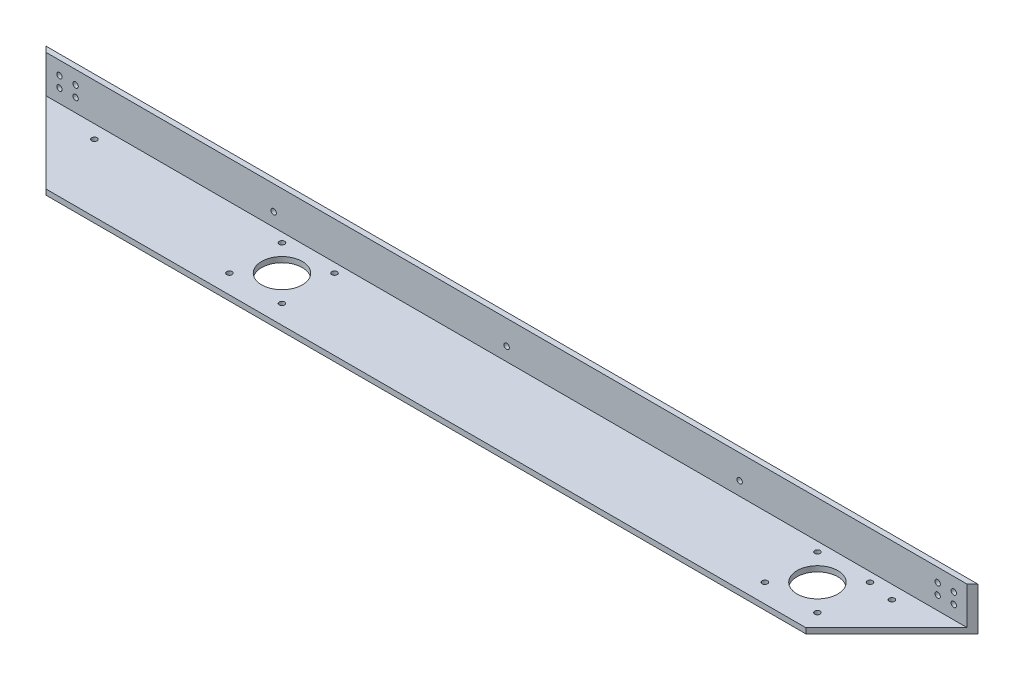
SolidWorks part; units mm, degrees
ref_plane "Front Plane" through (0, 0, 0) normal (0, 0, 1) x (1, 0, 0)
ref_plane "Top Plane" through (0, 0, 0) normal (0, 1, 0) x (1, 0, 0)
ref_plane "Right Plane" through (0, 0, 0) normal (1, 0, 0) x (0, 0, -1)
sketch "Sketch1" plane through (0, 0, 0) normal (1, 0, 0) x (0, 0, -1)
  line L0 (0, 0) -> (-50.8, 0)
  line L1 (-50.8, 0) -> (-50.8, 3.175)
  line L2 (-50.8, 3.175) -> (-3.175, 3.175)
  line L3 (-3.175, 3.175) -> (-3.175, 25.4)
  line L4 (-3.175, 25.4) -> (0, 25.4)
  line L5 (0, 25.4) -> (0, 0)
  dimension "LHeight" = 25.4
  dimension "LWidth" = 50.8
  dimension "LMaterialThickness" = 3.175
  dimension "D1" = 47.625
  dimension "D2" = 22.225
  dimension "D3" = 3.175
extrude "Boss-Extrude1" add sketch "Sketch1" along normal blind 550
chamfer "Chamfer7" distance 50.8 angle 45 1 edges at (0, 1.5875, 50.8)
chamfer "Chamfer8" distance 50.8 angle 45 1 edges at (550, 1.5875, 50.8)
sketch "BotthomHoles-Sketch2" plane through (0, 3.175, 0) normal (0, 1, 0) x (1, 0, 0)
  line L0 (546.825, -3.175) -> (3.175, -3.175) construction
  line L1 (550, 0) -> (0, 0) construction
  circle A0 centre (479.425, -24.175) radius 12
  circle A2 centre (463.925, -8.675) radius 1.5875
  circle A3 centre (494.925, -8.675) radius 1.5875
  circle A6 centre (463.925, -39.675) radius 1.5875
  circle A7 centre (494.925, -39.675) radius 1.5875
  circle A8 centre (39.6875, -11.1125) radius 1.5875
  circle A9 centre (510.3125, -11.1125) radius 1.5875
  circle A10 centre (178.925, -39.675) radius 1.5875
  circle A11 centre (147.925, -39.675) radius 1.5875
  circle A12 centre (178.925, -8.675) radius 1.5875
  circle A13 centre (147.925, -8.675) radius 1.5875
  circle A14 centre (163.425, -24.175) radius 12
  dimension "D9" = 3.175
  dimension "D10" = 24
  dimension "D13" = 3.175
  dimension "D2" = 8.675
  dimension "D5" = 15.5
  dimension "D6" = 31
  dimension "D7" = 15.5
  dimension "D8" = 31
  dimension "D11" = 21
  dimension "D3" = 70.575
  dimension "D4" = 11.1125
  dimension "D12" = 39.6875
  dimension "D14" = 39.6875
  dimension "D15" = 31
  dimension "D16" = 15.5
  dimension "D17" = 316
extrude "BottomHoles-Cut-Extrude1" cut sketch "BotthomHoles-Sketch2" against normal through all
sketch "SideHoles-Sketch3" plane through (0, 0, 0) normal (0, 0, -1) x (-1, 0, 0)
  line L0 (-550, 0) -> (-550, 25.4) construction
  circle A0 centre (-538.8875, 17.4625) radius 1.5875
  circle A1 centre (-529.3625, 17.4625) radius 1.5875
  circle A2 centre (-538.8875, 11.1125) radius 1.5875
  circle A3 centre (-529.3625, 11.1125) radius 1.5875
  circle A4 centre (-11.1125, 11.1125) radius 1.5875
  circle A5 centre (-20.6375, 11.1125) radius 1.5875
  circle A6 centre (-20.6375, 17.4625) radius 1.5875
  circle A7 centre (-11.1125, 17.4625) radius 1.5875
  circle A8 centre (-412.5, 11.1125) radius 1.5875
  circle A9 centre (-275, 11.1125) radius 1.5875
  circle A10 centre (-137.5, 11.1125) radius 1.5875
  dimension "D4" = 11.1125
  dimension "D7" = 3.175
  dimension "D1" = 11.1125
  dimension "D2" = 20.6375
  dimension "D3" = 7.9375
  dimension "D5" = 11.1125
  dimension "D6" = 20.6375
  dimension "D8" = 137.5
  dimension "D9" = 137.5
  dimension "D10" = 137.5
extrude "SideHoles-Cut-Extrude2" cut sketch "SideHoles-Sketch3" against normal through all
equation "\"LowerRailWidth\"= 2.00in"
equation "\"LowerRailHeight\"= 1.00in"
equation "\"RailThickness\"= .125in'Spec"
equation "\"SideRailHoleY1FromEdge\"= \"HoleOffsetFromEdge\""
equation "\"SideRailHoleX1FromSide\"= \"HoleOffsetFromSide\""
equation "\"StepperHoleDiameter\"= 24mm"
equation "\"StepperMountingHoleDiameter\"= 3.175mm"
equation "\"SideRailLength\"= 550mm"
equation "\"StepperMountingHoleDistance\"= 31mm'Spec"
equation "\"VSWidth\"= 1.25in'Spec"
equation "\"StepperMountingHoleOffsetFromLeftOrRightSide\"= \"StepperMountingHoleOffsetFromItsSide\" + \"RailThickness\""
equation "\"HoleOffsetFromEdge\"= \"RailThickness\" * 2.5"
equation "\"HoleOffsetFromSide\"= \"RailThickness\" * 3.5"
equation "\"StepperMountingHoleOffsetFromItsSide\"= 5.5mm'Spec"
equation "\"SideRailHoleX2FromSide\"= \"VSWidth\" - \"HoleOffsetFromEdge\" - \"RailThickness\"'Equals 20.6375"
equation "\"FasteningHoleDiameter\"= .125in"
equation "\"SideRailHoleY2FromSide\"= \"HoleOffsetFromSide\""
equation "\"LHeight@Sketch1\"=\"LowerRailHeight\""
equation "\"LWidth@Sketch1\"=\"LowerRailWidth\""
equation "\"D1@Chamfer7\"=\"LowerRailWidth\""
equation "\"D1@Chamfer8\"=\"LowerRailWidth\""
equation "\"D2@BotthomHoles-Sketch2\" = \"StepperMountingHoleOffsetFromLeftOrRightSide\""
equation "\"D5@BotthomHoles-Sketch2\" = \"StepperMountingHoleDistance\" / 2"
equation "\"D6@BotthomHoles-Sketch2\" = \"StepperMountingHoleDistance\""
equation "\"D7@BotthomHoles-Sketch2\" = \"StepperMountingHoleDistance\" / 2"
equation "\"D8@BotthomHoles-Sketch2\" = \"StepperMountingHoleDistance\""
equation "\"D9@BotthomHoles-Sketch2\" = \"StepperMountingHoleDiameter\""
equation "\"D10@BotthomHoles-Sketch2\" = \"StepperHoleDiameter\""
equation "\"D1@SideHoles-Sketch3\" = \"SideRailHoleX1FromSide\""
equation "\"D2@SideHoles-Sketch3\" = \"SideRailHoleX2FromSide\""
equation "\"D3@SideHoles-Sketch3\" = \"SideRailHoleY1FromEdge\""
equation "\"D4@SideHoles-Sketch3\" = \"SideRailHoleY2FromSide\""
equation "\"D7@SideHoles-Sketch3\" = \"FasteningHoleDiameter\""
equation "\"D1@Boss-Extrude1\"=\"SideRailLength\""
equation "\"D5@SideHoles-Sketch3\"=\"SideRailHoleX1FromSide\""
equation "\"D6@SideHoles-Sketch3\"=\"SideRailHoleX2FromSide\""
equation "\"BedOverlap\"= 20mm"
equation "\"BedThirdSize\"= 70mm"
equation "\"BedInnerSquareWidth\"= \"BedThirdSize\" * 3'Equals 210"
equation "\"BedInnerSquareLength\"= \"BedInnerSquareWidth\""
equation "\"BedLWidth\"= \"BedThirdSize\" + \"BedOverlap\"'Equals 90"
equation "\"BedLength\"= \"BedInnerSquareLength\" + \"BedLWidth\" * 2 - \"BedOverlap\" * 2 + \"BedIncreasedByLength\"'Equals 350"
equation "\"DistanceBetweenFrontToBackStepperHoles\"= \"BedLength\" - \"DistanceFromBedFrontToFirstLeftStepperHole\"'Equals 316"
equation "\"D3@BotthomHoles-Sketch2\"=\"DistanceFromFrontSideToFirstLeftStepperHole\""
equation "\"DistanceFromBedFrontToFirstLeftStepperHole\"= \"LeadScrewNutPadSize\" + 10mm'Equals 34"
equation "\"DistanceFromFrontSideToBedFront\"= \"RailThickness\" + \"BeltTensionerDepth\" + 10mm'Equals 36.575"
equation "\"20TGT2PulleyDiameter\"= 17.9mm'Spec"
equation "\"BeltTensionerBackWallThickness\"= 4mm"
equation "\"BeltTensionerSpaceBetweenPulleyAndWall\"= 1.5mm"
equation "\"BeltTensionerInnerDepth\"= \"20TGT2PulleyDiameter\" + \"BeltTensionerSpaceBetweenPulleyAndWall\""
equation "\"BeltTensionerDepth\"= \"BeltTensionerBackWallThickness\" + \"BeltTensionerInnerDepth\"'Equals 23.4"
equation "\"BedIncreasedByLength\"= 0mm"
equation "\"LowerCornerBlockWidth\"= \"LowerRailWidth\" - \"RailThickness\" * 2'Room for left front stepper"
equation "\"D4@BotthomHoles-Sketch2\"=\"LowerCornerBlockY1FromSide\""
equation "\"D12@BotthomHoles-Sketch2\"=\"LowerCornerBlockX1FromSide\""
equation "\"D13@BotthomHoles-Sketch2\"=\"FasteningHoleDiameter\""
equation "\"D14@BotthomHoles-Sketch2\"=\"LowerCornerBlockX1FromSide\""
equation "\"LowerCornerBlockX1FromSide\"= \"LowerCornerBlockWidth\" - \"HoleOffsetFromEdge\" + \"RailThickness\""
equation "\"LowerCornerBlockY1FromSide\"= \"HoleOffsetFromSide\""
equation "\"D15@BotthomHoles-Sketch2\"=\"StepperMountingHoleDistance\""
equation "\"D16@BotthomHoles-Sketch2\"=\"StepperMountingHoleDistance\"/2"
equation "\"D17@BotthomHoles-Sketch2\"=\"DistanceBetweenFrontToBackStepperHoles\""
equation "\"DistanceFromFrontSideToFirstLeftStepperHole\"= \"DistanceFromFrontSideToBedFront\" + \"DistanceFromBedFrontToFirstLeftStepperHole\"'Equals 70.575"
equation "\"LeadScrewNutMountingHoleFlangeDiameter\"= 22mm'Spec"
equation "\"LeadScrewNutPadSize\"= \"LeadScrewNutMountingHoleFlangeDiameter\" + 2mm'Equals 24"
equation "\"LeftOrRightEnclosureOffsets\"= \"SideRailLength\" / 4"
equation "\"D8@SideHoles-Sketch3\"=\"LeftOrRightEnclosureOffsets\""
equation "\"D9@SideHoles-Sketch3\"=\"LeftOrRightEnclosureOffsets\""
equation "\"D10@SideHoles-Sketch3\"=\"LeftOrRightEnclosureOffsets\""
